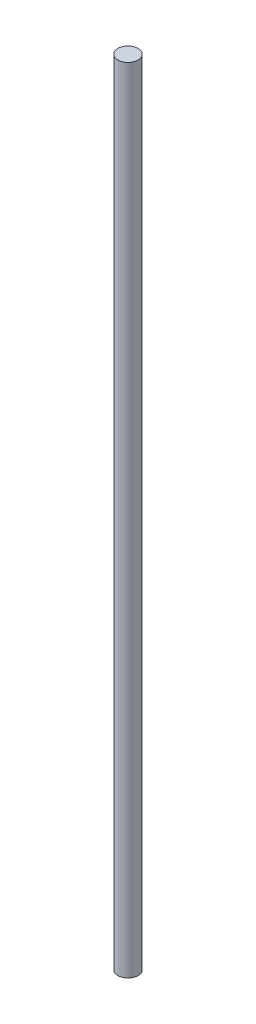
SolidWorks part; units mm, degrees
material "Plain Carbon Steel"
ref_plane "Front Plane" through (0, 0, 0) normal (0, 0, 1) x (1, 0, 0)
ref_plane "Top Plane" through (0, 0, 0) normal (0, 1, 0) x (1, 0, 0)
ref_plane "Right Plane" through (0, 0, 0) normal (1, 0, 0) x (0, 0, -1)
sketch "Sketch1" plane through (0, 0, 0) normal (0, 1, 0) x (1, 0, 0)
  circle A0 centre (0, 0) radius 4.7625
  dimension "D1" = 9.525
extrude "Boss-Extrude1" add sketch "Sketch1" along normal blind 374.65
equation "\"Mid_Coupler_Length\"= 13in"
equation "\"Lead_Screw_Length\"= (\"Mid_Coupler_Length\" + 2*0.375in + 2*0.5in)"
equation "\"D1@Boss-Extrude1\"=\"Lead_Screw_Length\""
